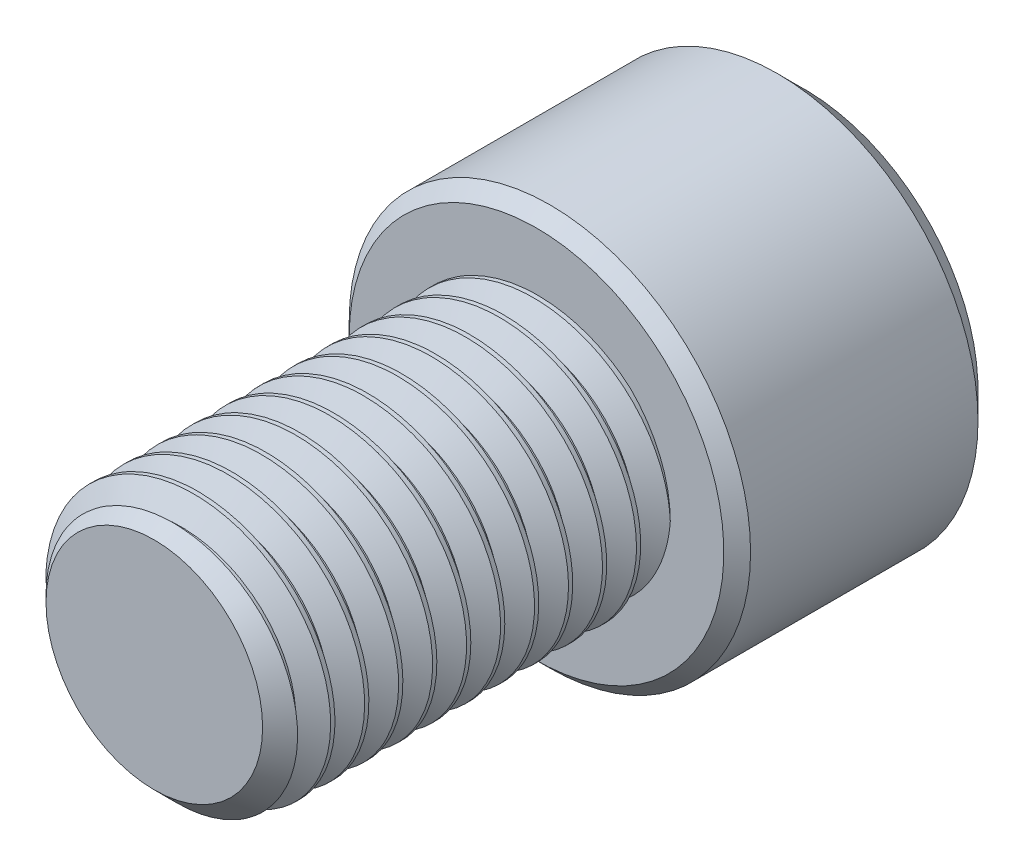
SolidWorks part; units mm, degrees
material "Plain Carbon Steel"
ref_plane "Front Plane" through (0, 0, 0) normal (0, 0, 1) x (1, 0, 0)
ref_plane "Top Plane" through (0, 0, 0) normal (0, 1, 0) x (1, 0, 0)
ref_plane "Right Plane" through (0, 0, 0) normal (1, 0, 0) x (0, 0, -1)
sketch "Sketch1" plane through (0, 0, 0) normal (0, 0, 1) x (1, 0, 0)
  line L0 (0, 11.1125) -> (0, -11.1125) construction
  circle A0 centre (0, 0) radius 11.1125
  dimension "OD" = 22.225
extrude "Extrude1" add sketch "Sketch1" against normal blind 31.75
sketch "Sketch2" plane through (0, 0, 0) normal (0, 0, 1) x (1, 0, 0)
  circle A0 centre (0, 0) radius 11.1125 construction
  circle A1 centre (0, 0) radius 11.1125
curve "Helix/Spiral1" pitch 2.8222 height 34.5722 turns 12.25 parameters "pitch"=2.8222
chamfer "Chamfer3" distance 2.1167 angle 45 1 edges at (11.1125, 0, 0)
sketch "Sketch3" plane through (0, 0, 0) normal (1, 0, 0) x (0, 0, -1)
  line L0 (-2.4694, 11.1125) -> (-1.4111, 9.2794)
  line L1 (-1.4111, 9.2794) -> (-1.0583, 9.2794)
  line L2 (-1.0583, 9.2794) -> (0, 11.1125)
  line L3 (-2.4694, 11.1125) -> (0, 11.1125)
  line L4 (-1.2347, 11.1125) -> (-1.2347, 9.2794) construction
  line L5 (-1.9403, 10.196) -> (-0.5292, 10.196) construction
  line L6 (0, 11.1125) -> (0, -11.1125) construction
  dimension "D1" = 0.3528
  dimension "D2" = 1.4111
  dimension "D3" = 60
sweep "Cut-Sweep1" cut profiles "Sketch3" path "Helix/Spiral1"
sketch "Sketch6" plane through (0, 0, -31.75) normal (0, 0, -1) x (-1, 0, 0)
  circle A0 centre (0, 0) radius 16.6687
  dimension "head dia" = 33.3375
extrude "Extrude2" add sketch "Sketch6" along normal blind 22.225
sketch "Sketch7" plane through (0, 0, -53.975) normal (0, 0, -1) x (-1, 0, 0)
  line L1 (0, 10.9985) -> (-9.525, 5.4993)
  line L2 (-9.525, 5.4993) -> (-9.525, -5.4993)
  line L3 (-9.525, -5.4993) -> (0, -10.9985)
  line L4 (0, -10.9985) -> (9.525, -5.4993)
  line L5 (9.525, -5.4993) -> (9.525, 5.4993)
  line L6 (9.525, 5.4993) -> (0, 10.9985)
  circle A0 centre (0, 0) radius 9.525 construction
  dimension "hex dia" = 19.05
extrude "Cut-Extrude1" cut sketch "Sketch7" against normal blind 14.2875
sketch "Sketch8" plane through (0, 0, -53.975) normal (0, 0, -1) x (-1, 0, 0)
  circle A0 centre (0, 0) radius 10.9985
extrude "Cut-Extrude2" cut sketch "Sketch8" against normal blind 2.2225 draft 45
chamfer "Chamfer1" distance 2.2225 angle 45 1 edges at (-16.6687, 0, -53.975)
chamfer "Chamfer2" distance 1.1112 angle 45 1 edges at (-16.6687, 0, -31.75)
sketch "Sketch9" plane through (0, 0, 0) normal (1, 0, 0) x (0, 0, -1)
  line L0 (0, 11.1125) -> (0, -11.1125) construction
  line L1 (15.5222, 11.1125) -> (15.5222, -11.1125) construction
  line L2 (31.75, 16.6687) -> (31.75, -16.6688) construction
  line L3 (53.975, 16.6687) -> (53.975, -16.6687) construction
  line L4 (53.975, 0) -> (0, 0) construction
  dimension "D1" = 15.5222
  dimension "D2" = 22.225
  dimension "D3" = 33.3375
  dimension "D4" = 31.75
equation "\"D3@Helix/Spiral1\" = \"screw length@Extrude1\"+\"pitch@Helix/Spiral1\""
equation "\"D1@Sketch3\" = \"pitch@Helix/Spiral1\"*.125"
equation "\"D2@Sketch3\" = \"pitch@Helix/Spiral1\"*.5"
equation "\"D1@Cut-Extrude1\" = \"hex dia@Sketch7\"*.75"
equation "\"D1@Chamfer1\" = \"head depth@Extrude2\"/10"
equation "\"D1@Sketch9\" = \"pitch@Helix/Spiral1\"*5.5"
equation "\"D1@Chamfer2\" = \"D1@Chamfer1\"/2"
equation "\"D1@Cut-Extrude2\" = \"D1@Chamfer2\"*2"
equation "\"D1@Chamfer3\" = \"pitch@Helix/Spiral1\"*.750"
equation "\"D2@Sketch9\" = \"head depth@Extrude2\""
equation "\"D3@Sketch9\" = \"head dia@Sketch6\""
equation "\"D4@Sketch9\" = \"screw length@Extrude1\""
